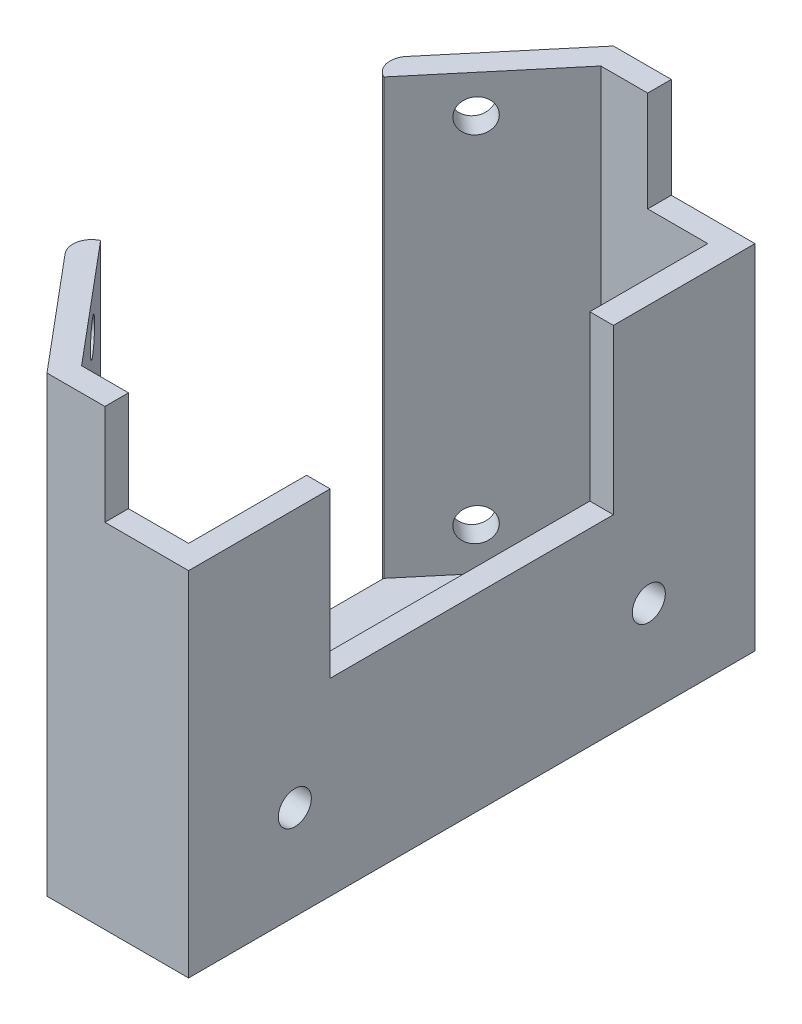
SolidWorks part; units mm, degrees
ref_plane "前视基准面" through (0, 0, 0) normal (0, 0, 1) x (1, 0, 0)
ref_plane "上视基准面" through (0, 0, 0) normal (0, 1, 0) x (1, 0, 0)
ref_plane "右视基准面" through (0, 0, 0) normal (1, 0, 0) x (0, 0, -1)
sketch "草图1" plane through (0, 0, 0) normal (0, 1, 0) x (1, 0, 0)
  line L0 (0, 0) -> (-7.5, 0) construction
  line L1 (-7.5, 30) -> (7.5, 30)
  line L2 (-7.5, 30) -> (-7.5, -30)
  line L3 (-7.5, -30) -> (7.5, -30)
  line L4 (7.5, 30) -> (7.5, -30)
  line L5 (-7.5, 30) -> (7.5, -30) construction
  line L6 (-7.5, -30) -> (7.5, 30) construction
  line L7 (-7.5, 0) -> (-39.415, 0) construction
  line L8 (-7.5, 30) -> (-32.673, 0)
  line L9 (-32.673, 0) -> (-7.5, -30)
  point P0 (0, 0)
  dimension "D1" = 100
  dimension "D2" = 60
  dimension "D3" = 15
extrude "凸台-拉伸1" add sketch "草图1" along normal blind 55 contours L8 L9 L2 | L4 L1 L2 L3 region at (0, 0, 0) region at (-15.891, 0, 0)
sketch "草图2" plane through (0, 55, 0) normal (0, 1, 0) x (1, 0, 0)
  line L0 (-32.673, 0) -> (7.5, 0) construction
  line L1 (7.5, 30) -> (7.5, -30) construction
  line L2 (-29.4095, 0) -> (-4.2365, 30)
  line L3 (-7.5, 30) -> (7.5, 30) construction
  line L4 (-7.5, 30) -> (-32.673, 0) construction
  line L5 (-29.4095, 0) -> (-4.2365, -30)
  line L6 (7.5, 27.5) -> (-6.3342, 27.5)
  line L7 (7.5, -27.5) -> (-6.3342, -27.5)
  line L8 (5, 27.5) -> (5, -27.5)
  line L9 (-6.3342, 27.5) -> (-29.4095, 0)
  line L10 (-29.4095, 0) -> (-24.9649, 0.153)
  line L11 (-6.3342, -27.5) -> (5, -27.5)
  line L12 (5, 27.5) -> (-6.3342, 27.5)
  dimension "D1" = 2.5
  dimension "D2" = 2.5
  dimension "D3" = 2.5
extrude "切除-拉伸1" cut sketch "草图2" against normal blind 53 contours L0 L8 L6 L2 | L0 L5 L7 L8 region at (-7.4059, 55, -11.438) region at (-7.4059, 55, 11.438)
sketch "草图3" plane through (0, 55, 0) normal (0, 1, 0) x (1, 0, 0)
  line L0 (-32.673, 0) -> (7.5, 0) construction
  line L1 (7.5, 30) -> (7.5, -30) construction
  line L3 (-51.8697, 15) -> (26.6967, 15)
  line L4 (-51.8697, 15) -> (-51.8697, -15)
  line L5 (-51.8697, -15) -> (26.6967, -15)
  line L6 (26.6967, 15) -> (26.6967, -15)
  line L7 (-51.8697, 15) -> (26.6967, -15) construction
  line L8 (-51.8697, -15) -> (26.6967, 15) construction
  point P5 (-12.5865, 0)
  dimension "D1" = 30
extrude "切除-拉伸2" cut sketch "草图3" against normal blind 35
sketch "草图4" plane through (0, 20, 0) normal (0, 1, 0) x (1, 0, 0)
  line L0 (-16.823, 15) -> (-73.5845, 15)
  line L1 (-73.5845, 15) -> (-53.8246, -15)
  line L2 (-53.8246, -15) -> (-16.823, -15)
  line L3 (-16.823, -15) -> (-16.823, 15)
extrude "切除-拉伸3" cut sketch "草图4" against normal blind 25
fillet "圆角1" radius 2 2 edges at (-20.0865, 27.5, 15) (-20.0865, 27.5, -15)
sketch "草图5" plane through (-19.1733, 0, 16.0883) normal (-0.766, 0, 0.6428) x (0.6428, 0, 0.766)
  line L0 (2.6136, 55) -> (18.1604, 55) construction
  line L1 (2.6136, 55) -> (2.6136, 0) construction
  circle A0 centre (7.6136, 44) radius 1.75
  circle A1 centre (6.6136, 6.5133) radius 1.75
  dimension "D2" = 37.5
  dimension "D1" = 11
  dimension "D3" = 5
  dimension "D4" = 4
extrude "切除-拉伸4" cut sketch "草图5" against normal blind 3 contours A1 | A0
sketch "草图6" plane through (-19.1733, 0, -16.0883) normal (-0.766, 0, -0.6428) x (-0.6428, 0, 0.766)
  line L0 (-7.6136, 55) -> (-7.6136, 0) construction
  line L1 (-18.1604, 55) -> (-2.6136, 55) construction
  line L2 (-18.1604, 0) -> (-2.6136, 0) construction
  line L3 (-2.6136, 0) -> (-2.6136, 55) construction
  circle A0 centre (-7.6136, 44) radius 1.75
  circle A1 centre (-7.6136, 6.5) radius 1.75
  dimension "D2" = 11
  dimension "D1" = 5
  dimension "D3" = 37.5
extrude "切除-拉伸5" cut sketch "草图6" against normal blind 3
sketch "草图7" plane through (7.5, 0, 0) normal (1, 0, 0) x (0, 0, -1)
  line L0 (0, 20) -> (0, 0) construction
  line L1 (15, 20) -> (-15, 20) construction
  line L2 (30, 0) -> (-30, 0) construction
  circle A0 centre (18.75, 10) radius 1.75
  circle A1 centre (-18.75, 10) radius 1.75
  dimension "D1" = 37.5
  dimension "D2" = 10
extrude "切除-拉伸6" cut sketch "草图7" against normal blind 3
sketch "草图8" plane through (7.5, 0, 0) normal (1, 0, 0) x (0, 0, -1)
  line L0 (30, 55) -> (30, 0) construction
  line L1 (-30, 55) -> (30, 55)
  line L2 (-30, 55) -> (-30, 48)
  line L3 (-30, 48) -> (30, 48)
  line L4 (30, 55) -> (30, 48)
extrude "切除-拉伸7" cut sketch "草图8" against normal through all
sketch "草图9" plane through (0, 2, 0) normal (0, 1, 0) x (1, 0, 0)
  line L0 (-0.6671, 27.5) -> (-0.6671, -27.5) construction
  line L1 (5, 27.5) -> (-6.3342, 27.5) construction
  line L2 (5, -27.5) -> (-6.3342, -27.5) construction
  line L3 (5, 27.5) -> (-6.3342, 27.5) construction
  line L4 (5, -27.5) -> (-6.3342, -27.5) construction
  circle A0 centre (-0.6671, -23.5) radius 1.75
  circle A1 centre (-0.6671, 23.5) radius 1.75
  dimension "D1" = 4
  dimension "D2" = 4
extrude "切除-拉伸8" cut sketch "草图9" against normal blind 10
sketch "草图10" plane through (0, 0, 30) normal (0, 0, 1) x (1, 0, 0)
  line L0 (-1.3675, 48) -> (7.5, 48)
  line L1 (-1.3675, 48) -> (-1.3675, 37.3718)
  line L2 (-1.3675, 37.3718) -> (7.5, 37.3718)
  line L3 (7.5, 48) -> (7.5, 0) construction
  line L4 (7.5, 37.3718) -> (7.5, 48)
  line L5 (-7.5, 48) -> (7.5, 48) construction
extrude "切除-拉伸9" cut sketch "草图10" against normal blind 78
